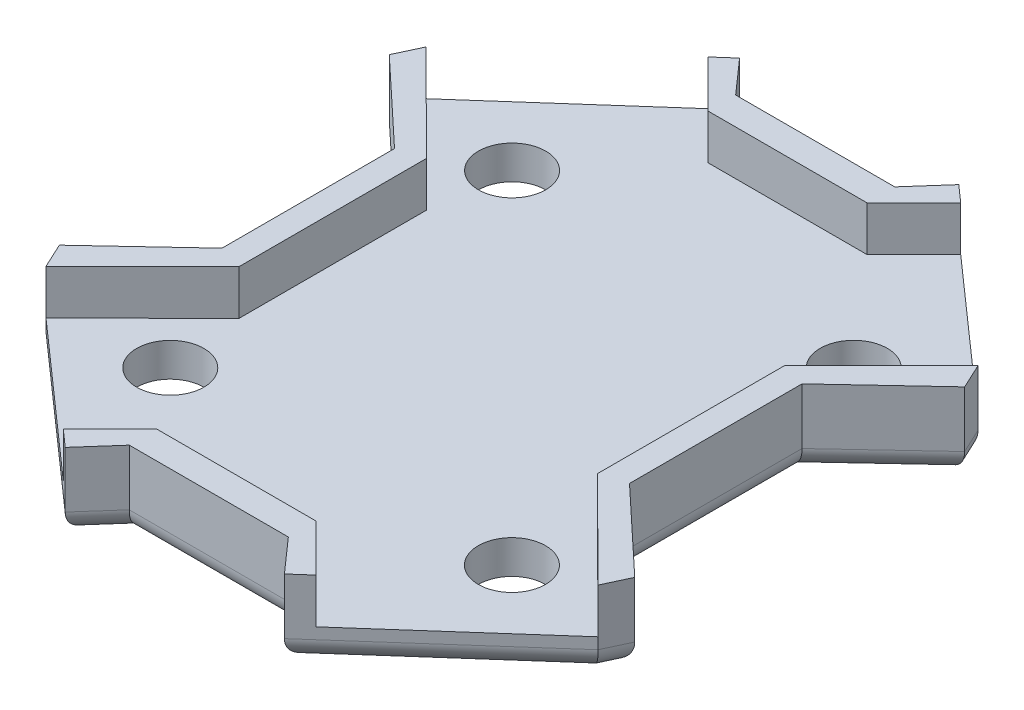
SolidWorks part; units mm, degrees
ref_plane "Front Plane" through (0, 0, 0) normal (0, 0, 1) x (1, 0, 0)
ref_plane "Top Plane" through (0, 0, 0) normal (0, 1, 0) x (1, 0, 0)
ref_plane "Right Plane" through (0, 0, 0) normal (1, 0, 0) x (0, 0, -1)
sketch "Sketch1" plane through (0, 0, 0) normal (0, 1, 0) x (1, 0, 0)
  line L1 (27.5, -32.215) -> (-27.5, -32.215)
  line L2 (27.5, -32.215) -> (27.5, 32.215)
  line L3 (27.5, 32.215) -> (-27.5, 32.215)
  line L4 (-27.5, -32.215) -> (-27.5, 32.215)
  line L5 (27.5, -32.215) -> (-27.5, 32.215) construction
  line L6 (27.5, 32.215) -> (-27.5, -32.215) construction
  point P0 (0, 0)
  dimension "D1" = 64.43
  dimension "D2" = 55
extrude "Boss-Extrude1" add sketch "Sketch1" along normal blind 3
sketch "Sketch2" plane through (0, 3, 0) normal (0, 1, 0) x (1, 0, 0)
  line L0 (-27.5, -32.215) -> (-27.5, 0) construction
  line L1 (-27.5, 32.215) -> (-27.5, -32.215) construction
  line L2 (-27.5, -32.215) -> (0, -32.215) construction
  line L3 (-27.5, -32.215) -> (27.5, -32.215) construction
  line L4 (-27.5, -4.7913) -> (-27.5, -14.3738)
  line L5 (-27.5, 0) -> (-17.5, 0) construction
  line L6 (-27.5, 4.7913) -> (-27.5, -4.7913)
  line L8 (-17.5, 5) -> (-17.5, -5)
  line L9 (-27.5, -14.3738) -> (-17.5, -5)
  line L10 (0, -32.215) -> (0, 32.215) construction
  line L11 (27.5, 32.215) -> (-27.5, 32.215) construction
  line L12 (-27.5, 14.3738) -> (-17.5, 5)
  line L13 (-27.5, 4.7913) -> (-27.5, 14.3738)
  line L14 (27.5, 4.7913) -> (27.5, 14.3738)
  line L15 (27.5, 14.3738) -> (17.5, 5)
  line L16 (27.5, 4.7913) -> (27.5, -4.7913)
  line L17 (27.5, 0) -> (17.5, 0) construction
  line L18 (17.5, 5) -> (17.5, -5)
  line L19 (27.5, -14.3738) -> (17.5, -5)
  line L20 (27.5, -4.7913) -> (27.5, -14.3738)
  dimension "D1" = 10
  dimension "D2" = 5
extrude "Cut-Extrude1" cut sketch "Sketch2" against normal blind 4
sketch "Sketch3" plane through (0, 3, 0) normal (0, 1, 0) x (1, 0, 0)
  line L0 (-27.5, 14.3738) -> (27.5, 14.3738) construction
  line L1 (0, -32.215) -> (0, 32.215) construction
  line L2 (-27.5, -32.215) -> (27.5, -32.215) construction
  line L3 (27.5, 32.215) -> (-27.5, 32.215) construction
  line L4 (-17.5, 0) -> (17.5, 0) construction
  line L5 (-17.5, -5) -> (-17.5, 5) construction
  line L6 (17.5, 5) -> (17.5, -5) construction
  line L7 (-27.5, 14.3738) -> (-25.8679, 17.8738)
  line L8 (-17.5, 5) -> (-17.5, 0)
  line L9 (-25.8679, 17.8738) -> (27.5, 17.8738) construction
  line L10 (27.5, 14.3738) -> (27.5, 32.215) construction
  line L11 (-25.8679, 17.8738) -> (-25.8679, 32.215) construction
  line L12 (-25.8679, 17.8738) -> (-9.6529, 32.215)
  line L13 (-9.6529, 32.215) -> (-3.7424, 25.5322)
  line L14 (-3.7424, 25.5322) -> (3.7424, 25.5322)
  line L15 (9.6529, 32.215) -> (3.7424, 25.5322)
  line L16 (25.8679, 17.8738) -> (9.6529, 32.215)
  line L17 (27.5, 14.3738) -> (25.8679, 17.8738)
  line L27 (-17.5, 5) -> (-27.5, 14.3738)
  line L30 (17.5, 5) -> (27.5, 14.3738)
  line L31 (17.5, 5) -> (17.5, -5)
  line L32 (17.5, -5) -> (27.5, -14.3738)
  line L33 (27.5, -14.3738) -> (25.8679, -17.8738)
  line L34 (25.8679, -17.8738) -> (9.6529, -32.215)
  line L35 (9.6529, -32.215) -> (3.7424, -25.5322)
  line L36 (-3.7424, -25.5322) -> (3.7424, -25.5322)
  line L37 (-9.6529, -32.215) -> (-3.7424, -25.5322)
  line L38 (-25.8679, -17.8738) -> (-9.6529, -32.215)
  line L39 (-27.5, -14.3738) -> (-25.8679, -17.8738)
  line L40 (-17.5, -5) -> (-27.5, -14.3738)
  line L41 (-17.5, -5) -> (-17.5, 0)
  line L42 (-16, -5.6499) -> (-16, 0)
  line L43 (-16, 5.6499) -> (-16, 0)
  line L44 (-16, 5.6499) -> (-25.6812, 14.7249)
  line L45 (-25.6812, 14.7249) -> (-24.6404, 16.957)
  line L46 (-24.6404, 16.957) -> (-9.7828, 30.0977)
  line L47 (-9.7828, 30.0977) -> (-4.4183, 24.0322)
  line L48 (-4.4183, 24.0322) -> (4.4183, 24.0322)
  line L49 (9.7828, 30.0977) -> (4.4183, 24.0322)
  line L50 (24.6404, 16.957) -> (9.7828, 30.0977)
  line L51 (25.6812, 14.7249) -> (24.6404, 16.957)
  line L52 (16, 5.6499) -> (25.6812, 14.7249)
  line L53 (16, 5.6499) -> (16, -5.6499)
  line L54 (16, -5.6499) -> (25.6812, -14.7249)
  line L55 (25.6812, -14.7249) -> (24.6404, -16.957)
  line L56 (24.6404, -16.957) -> (9.7828, -30.0977)
  line L57 (9.7828, -30.0977) -> (4.4183, -24.0322)
  line L58 (-4.4183, -24.0322) -> (4.4183, -24.0322)
  line L59 (-9.7828, -30.0977) -> (-4.4183, -24.0322)
  line L60 (-24.6404, -16.957) -> (-9.7828, -30.0977)
  line L61 (-25.6812, -14.7249) -> (-24.6404, -16.957)
  line L62 (-16, -5.6499) -> (-25.6812, -14.7249)
  point P27 (0, 23.6915)
  dimension "D1" = 1.5
  dimension "D2" = 3.5
extrude "Cut-Extrude4" cut sketch "Sketch3" against normal blind 4 flip side to cut contours L42 L43 L44 L45 L46 L47 L48 L49 L50 L51 L52 L53 L54 L55 L56 L57 L58 L59 L60 L61 L62
sketch "Sketch4" plane through (0, 3, 0) normal (0, 1, 0) x (1, 0, 0)
  line L0 (-7.1005, 27.0649) -> (7.1005, 27.0649)
  line L1 (-9.7828, 30.0977) -> (-4.4183, 24.0322) construction
  line L2 (9.7828, 30.0977) -> (4.4183, 24.0322) construction
  line L3 (-7.1005, -27.0649) -> (7.1005, -27.0649)
  line L4 (-9.7828, -30.0977) -> (-4.4183, -24.0322) construction
  line L5 (9.7828, -30.0977) -> (4.4183, -24.0322) construction
  line L6 (7.1005, -27.0649) -> (4.4183, -24.0322)
  line L7 (4.4183, -24.0322) -> (-4.4183, -24.0322)
  line L8 (-4.4183, -24.0322) -> (-7.1005, -27.0649)
  line L9 (-7.1005, 27.0649) -> (-4.4183, 24.0322)
  line L10 (-4.4183, 24.0322) -> (4.4183, 24.0322)
  line L11 (4.4183, 24.0322) -> (7.1005, 27.0649)
extrude "Boss-Extrude2" add sketch "Sketch4" against normal blind 3
sketch "Sketch5" plane through (0, 3, 0) normal (0, 1, 0) x (1, 0, 0)
  line L0 (-16, 5.6499) -> (-18.1887, 7.7016)
  line L1 (-16, 5.6499) -> (-25.6812, 14.7249) construction
  line L2 (-16, -5.6499) -> (-18.1887, -7.7016)
  line L3 (-16, -5.6499) -> (-25.6812, -14.7249) construction
  line L4 (-18.1887, 7.7016) -> (-18.1887, -7.7016)
  line L5 (-16, 5.6499) -> (-16, -5.6499)
  line L6 (0, 27.0649) -> (0, -27.0649) construction
  line L7 (7.1005, 27.0649) -> (-7.1005, 27.0649) construction
  line L8 (-7.1005, -27.0649) -> (7.1005, -27.0649) construction
  line L9 (16, 5.6499) -> (18.1887, 7.7016)
  line L10 (18.1887, 7.7016) -> (18.1887, -7.7016)
  line L11 (16, -5.6499) -> (18.1887, -7.7016)
  line L12 (16, 5.6499) -> (16, -5.6499)
  dimension "D1" = 3
  dimension "D2" = 3
extrude "Boss-Extrude3" add sketch "Sketch5" against normal blind 3
sketch "Sketch6" plane through (0, 3, 0) normal (0, 1, 0) x (1, 0, 0)
  line L0 (-24.6404, -16.957) -> (-25.6812, -14.7249)
  line L1 (-25.6812, -14.7249) -> (-18.1887, -7.7016)
  line L2 (-18.1887, -7.7016) -> (-18.1887, 7.7016)
  line L3 (-18.1887, 7.7016) -> (-25.6812, 14.7249)
  line L4 (-25.6812, 14.7249) -> (-24.6404, 16.957)
  line L5 (-24.6404, 16.957) -> (-16, 8.3734)
  line L6 (-16, 8.3734) -> (-16, -8.3734)
  line L7 (-16, -8.3734) -> (-24.6404, -16.957)
  line L8 (-18.1887, 7.7016) -> (-18.1887, -7.7016) construction
  line L9 (0, 27.0649) -> (0, -27.0649) construction
  line L10 (7.1005, 27.0649) -> (-7.1005, 27.0649) construction
  line L11 (-7.1005, -27.0649) -> (7.1005, -27.0649) construction
  line L12 (16, -8.3734) -> (24.6404, -16.957)
  line L13 (16, 8.3734) -> (16, -8.3734)
  line L14 (24.6404, 16.957) -> (16, 8.3734)
  line L15 (25.6812, 14.7249) -> (24.6404, 16.957)
  line L16 (18.1887, 7.7016) -> (25.6812, 14.7249)
  line L17 (18.1887, -7.7016) -> (18.1887, 7.7016)
  line L18 (25.6812, -14.7249) -> (18.1887, -7.7016)
  line L19 (24.6404, -16.957) -> (25.6812, -14.7249)
extrude "Boss-Extrude4" add sketch "Sketch6" along normal blind 4
sketch "Sketch7" plane through (0, 3, 0) normal (0, 1, 0) x (1, 0, 0)
  line L1 (-1, 27.0649) -> (-7.1005, 27.0649)
  line L2 (-7.1005, 27.0649) -> (-9.7828, 30.0977)
  line L3 (-9.7828, 30.0977) -> (-11.2809, 28.7727)
  line L4 (-1, 24.5949) -> (-7.1005, 24.5949)
  line L5 (-7.1005, 24.5949) -> (-11.2809, 28.7727)
  line L6 (0, 27.0649) -> (0, -27.0649) construction
  line L7 (7.1005, 27.0649) -> (-7.1005, 27.0649) construction
  line L8 (-7.1005, -27.0649) -> (7.1005, -27.0649) construction
  line L9 (-1, 27.0649) -> (1, 27.0649)
  line L10 (-1, 24.5949) -> (1, 24.5949)
  line L12 (1, 24.5949) -> (7.1005, 24.5949)
  line L13 (7.1005, 24.5949) -> (11.2809, 28.7727)
  line L14 (9.7828, 30.0977) -> (11.2809, 28.7727)
  line L15 (7.1005, 27.0649) -> (9.7828, 30.0977)
  line L16 (1, 27.0649) -> (7.1005, 27.0649)
  line L17 (-18.1887, 0) -> (18.1887, 0) construction
  line L18 (-18.1887, 7.7016) -> (-18.1887, -7.7016) construction
  line L19 (18.1887, -7.7016) -> (18.1887, 7.7016) construction
  line L20 (-1, -27.0649) -> (-7.1005, -27.0649)
  line L21 (-7.1005, -27.0649) -> (-9.7828, -30.0977)
  line L22 (-9.7828, -30.0977) -> (-11.2809, -28.7727)
  line L23 (-7.1005, -24.5949) -> (-11.2809, -28.7727)
  line L24 (-1, -24.5949) -> (-7.1005, -24.5949)
  line L25 (-1, -24.5949) -> (1, -24.5949)
  line L26 (1, -24.5949) -> (7.1005, -24.5949)
  line L27 (7.1005, -24.5949) -> (11.2809, -28.7727)
  line L28 (9.7828, -30.0977) -> (11.2809, -28.7727)
  line L29 (7.1005, -27.0649) -> (9.7828, -30.0977)
  line L30 (1, -27.0649) -> (7.1005, -27.0649)
  line L31 (-1, -27.0649) -> (1, -27.0649)
extrude "Boss-Extrude5" add sketch "Sketch7" along normal blind 4 contours L9 L16 L15 L14 L13 L12 L10 L4 L5 L3 L2 L1 | L20 L21 L22 L23 L24 L25 L26 L27 L28 L29 L30 L31
fillet "Fillet1" radius 2 20 edges at (25.1608, 0, -15.841) (21.935, 0, -11.2133) (18.1887, 0, 0) (21.935, 0, 11.2133) (25.1608, 0, 15.841) (17.2116, 0, 23.5273) (8.4416, 0, 28.5813) (0, 0, 27.0649) (-8.4416, 0, 28.5813) (-17.2116, 0, 23.5273) (-25.1608, 0, 15.841) (-21.935, 0, 11.2133) (-18.1887, 0, 0) (-25.1608, 0, -15.841) (-21.935, 0, -11.2133) (-17.2116, 0, -23.5273) (-8.4416, 0, -28.5813) (0, 0, -27.0649) (8.4416, 0, -28.5813) (17.2116, 0, -23.5273)
sketch "Sketch9" plane through (0, 3, 0) normal (0, 1, 0) x (1, 0, 0)
  line L0 (25.6812, -14.7249) -> (24.6404, -16.957) construction
  line L1 (25.6812, -14.7249) -> (15.2512, -15.2442) construction
  line L3 (15.2512, -15.2442) -> (-15.2488, -15.2442) construction
  line L4 (15.2512, -15.2442) -> (15.2512, 15.2558) construction
  line L5 (15.2512, 15.2558) -> (-15.2488, 15.2558) construction
  line L6 (-15.2488, -15.2442) -> (-15.2488, 15.2558) construction
  circle A0 centre (15.2512, -15.2442) radius 1.75
  circle A1 centre (15.2512, 15.2558) radius 1.75
  circle A2 centre (-15.2488, 15.2558) radius 1.75
  circle A3 centre (-15.2488, -15.2442) radius 1.75
  dimension "D5" = 3.5
  dimension "D6" = 3.5
  dimension "D7" = 3.5
  dimension "D8" = 3.5
  dimension "D1" = 62.15
  dimension "D2" = 10.43
  dimension "D3" = 30.5
  dimension "D4" = 30.5
extrude "Cut-Extrude6" cut sketch "Sketch9" against normal through all
sketch "Sketch10" plane through (0, 0, 0) normal (0, -1, 0) x (1, 0, 0)
  line L0 (-16.1887, 0) -> (16.1887, 0) construction
  line L1 (-16.1887, 8.5681) -> (-16.1887, -8.5681) construction
  line L2 (16.1887, -8.5681) -> (16.1887, 8.5681) construction
  line L3 (0, 25.0649) -> (0, -25.0649) construction
  line L4 (8.0016, 25.0649) -> (-8.0016, 25.0649) construction
  line L5 (-8.0016, -25.0649) -> (8.0016, -25.0649) construction
  circle A0 centre (-15.2488, -15.2558) radius 3
  circle A1 centre (-15.2488, 15.2558) radius 3
  circle A2 centre (15.2488, -15.2558) radius 3
  circle A3 centre (15.2488, 15.2558) radius 3
  dimension "D1" = 6
extrude "Cut-Extrude7" cut sketch "Sketch10" against normal blind 3
